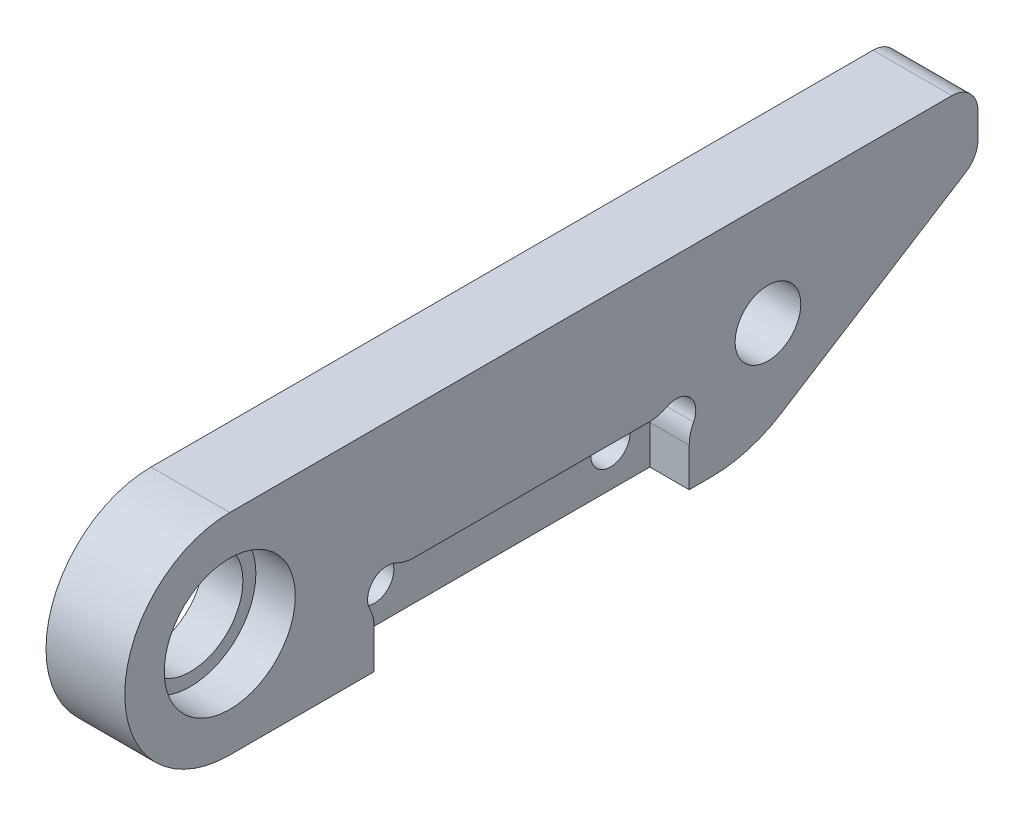
SolidWorks part; units mm, degrees
material "1060 Alloy"
ref_plane "Front Plane" through (0, 0, 0) normal (0, 0, 1) x (1, 0, 0)
ref_plane "Top Plane" through (0, 0, 0) normal (0, 1, 0) x (1, 0, 0)
ref_plane "Right Plane" through (0, 0, 0) normal (1, 0, 0) x (0, 0, -1)
sketch "Sketch27" plane through (0, 0, 0) normal (1, 0, 0) x (0, 0, -1)
  line L2 (9, 50) -> (66, 50)
  line L3 (9, 42) -> (30.9317, 42) construction
  line L4 (30.9317, 42) -> (30.9317, 54) construction
  line L6 (9, 34) -> (48.5644, 34)
  line L7 (30.9317, 54) -> (9, 42) construction
  line L8 (0, 0) -> (60, 0) construction
  line L9 (0, 0) -> (0, 58) construction
  line L10 (0, 58) -> (60, 58) construction
  line L11 (60, 0) -> (60, 58) construction
  line L12 (66, 50) -> (66, 45)
  line L13 (48.5644, 34) -> (66, 45)
  arc A0 (9, 50) -> (9, 34) centre (9, 42) ccw
  circle A1 centre (50, 42) radius 6 construction
  circle A3 centre (9, 42) radius 5.6 construction
  circle A5 centre (9, 42) radius 4
  circle A6 centre (50, 42) radius 2.5
  dimension "D9" = 12
  dimension "D10" = 5
  dimension "D12" = 8
  dimension "D13" = 8
  dimension "D14" = 5
  dimension "D6" = 16
  dimension "D16" = 11.2
  dimension "D1" = 60
  dimension "D2" = 58
  dimension "D3" = 42
  dimension "D4" = 9
  dimension "D5" = 50
  dimension "D7" = 42
  dimension "D8" = 12
  dimension "D17" = 25
extrude "Boss-Extrude1" add sketch "Sketch27" along normal blind 6
sketch "Sketch33" plane through (6, 0, 0) normal (1, 0, 0) x (0, 0, -1)
  circle A0 centre (9, 42) radius 4.99
  dimension "D1" = 9.98
extrude "Cut-Extrude2" cut sketch "Sketch33" against normal blind 3
sketch "Sketch34" plane through (6, 0, 0) normal (1, 0, 0) x (0, 0, -1)
  line L0 (20, 34) -> (44, 34)
  line L1 (20, 34) -> (20, 40)
  line L2 (44, 34) -> (44, 40)
  line L3 (20, 40) -> (44, 40)
  line L4 (9, 34) -> (48.5644, 34) construction
  circle A0 centre (50, 42) radius 2.5 construction
  dimension "D1" = 24
  dimension "D2" = 6
  dimension "D3" = 6
extrude "Cut-Extrude3" cut sketch "Sketch34" against normal blind 3
sketch "Sketch35" plane through (6, 0, 0) normal (1, 0, 0) x (0, 0, -1)
  line L0 (44, 40) -> (20, 40) construction
  line L1 (20, 40) -> (20, 34) construction
  line L2 (44, 34) -> (44, 40) construction
  line L3 (44, 40) -> (20, 40) construction
  circle A0 centre (21, 39) radius 1.5
  circle A1 centre (43, 39) radius 1.5
  dimension "D1" = 3
  dimension "D2" = 1
  dimension "D3" = 1
  dimension "D4" = 1
  dimension "D5" = 1
extrude "Cut-Extrude4" cut sketch "Sketch35" against normal up to surface (3 mm away) up to face at (3, 37, -32)
fillet "Fillet1" radius 3 4 edges at (4.5, 37.882, -44) (4.5, 40, -41.882) (4.5, 37.882, -20) (4.5, 40, -22.118)
sketch "Sketch36" plane through (3, 0, 0) normal (1, 0, 0) x (0, 0, -1)
  line L0 (20, 36.9384) -> (20, 34) construction
  line L1 (20, 34) -> (44, 34) construction
  line L2 (44, 34) -> (44, 36.9384) construction
  circle A0 centre (23, 37) radius 1.5
  circle A1 centre (41, 37) radius 1.5
  dimension "D1" = 3
  dimension "D2" = 3
  dimension "D3" = 3
  dimension "D4" = 3
  dimension "D5" = 3
extrude "Cut-Extrude5" cut sketch "Sketch36" against normal up to next
fillet "Fillet3" radius 2 2 edges at (3, 50, -66) (3, 45, -66)
fillet "Fillet4" radius 10 1 edges at (3, 34, -48.5644)
